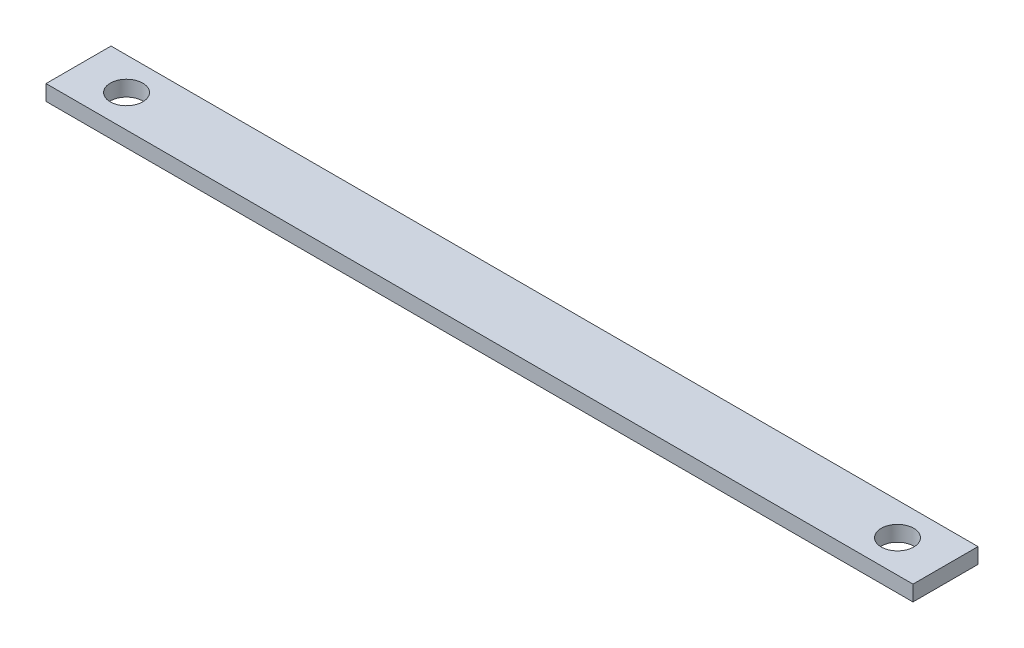
SolidWorks part; units mm, degrees
ref_plane "Plan de face" through (0, 0, 0) normal (0, 0, 1) x (1, 0, 0)
ref_plane "Plan de dessus" through (0, 0, 0) normal (0, 1, 0) x (1, 0, 0)
ref_plane "Plan de droite" through (0, 0, 0) normal (1, 0, 0) x (0, 0, -1)
sketch "Esquisse1" plane through (0, 0, 0) normal (0, 1, 0) x (1, 0, 0)
  line L1 (-280, -21) -> (280, -21)
  line L2 (-280, -21) -> (-280, 21)
  line L3 (-280, 21) -> (280, 21)
  line L4 (280, -21) -> (280, 21)
  line L5 (-280, -21) -> (280, 21) construction
  line L6 (-280, 21) -> (280, -21) construction
  point P0 (0, 0)
  dimension "D1" = 560
  dimension "D2" = 42
extrude "Boss.-Extru.1" add sketch "Esquisse1" along normal blind 10
sketch "Esquisse2" plane through (0, 10, 0) normal (0, 1, 0) x (1, 0, 0)
  line L0 (-218, 21) -> (-218, -21) construction
  line L2 (280, 21) -> (-280, 21) construction
  line L4 (-280, -21) -> (280, -21) construction
  line L5 (-218, 0) -> (-280, 0) construction
  line L6 (-280, 21) -> (-280, -21) construction
  line L8 (218, 21) -> (218, -21) construction
  line L9 (218, 0) -> (280, 0) construction
  line L10 (280, -21) -> (280, 21) construction
  circle A2 centre (249, 0) radius 10.5
  circle A3 centre (-249, 0) radius 10.5
  dimension "D1" = 62
  dimension "D2" = 21
  dimension "D4" = 21
  dimension "D3" = 62
extrude "Enlèv. mat.-Extru.1" cut sketch "Esquisse2" against normal blind 20
